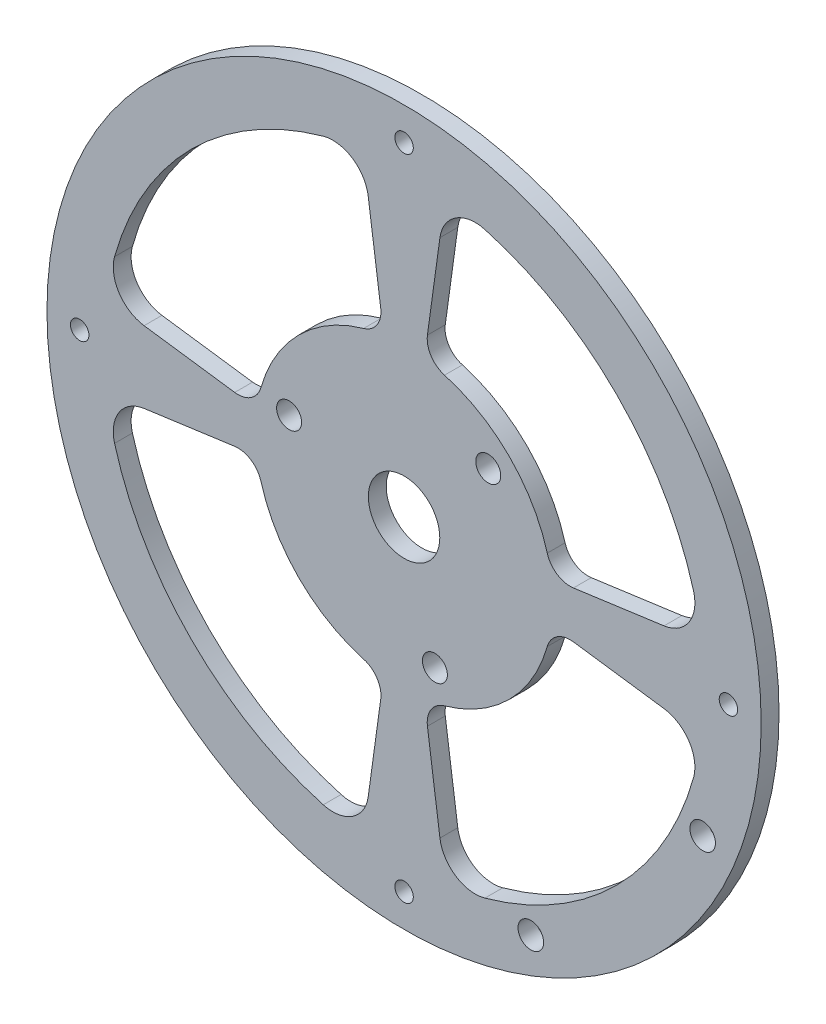
SolidWorks part; units mm, degrees
ref_plane "前视基准面" through (0, 0, 0) normal (0, 0, 1) x (1, 0, 0)
ref_plane "上视基准面" through (0, 0, 0) normal (0, 1, 0) x (1, 0, 0)
ref_plane "右视基准面" through (0, 0, 0) normal (1, 0, 0) x (0, 0, -1)
sketch "草图1" plane through (0, 0, 0) normal (0, 0, 1) x (1, 0, 0)
  line L0 (0, 0) -> (14.1421, 14.1421) construction
  line L1 (3.9232, -28.4536) -> (6.0227, -43.6804)
  line L2 (28.4536, 3.9232) -> (43.6804, 6.0227)
  line L3 (3.9232, 28.4536) -> (6.0227, 43.6804)
  line L4 (28.4536, -3.9232) -> (43.6804, -6.0227)
  line L5 (-28.4536, -3.9232) -> (-43.6804, -6.0227)
  line L6 (-3.9232, -28.4536) -> (-6.0227, -43.6804)
  line L7 (-3.9232, 28.4536) -> (-6.0227, 43.6804)
  line L8 (-28.4536, 3.9232) -> (-43.6804, 6.0227)
  circle A0 centre (0, 0) radius 60
  circle A1 centre (0, 54.5) radius 1.55
  circle A2 centre (-54.5, 0) radius 1.55
  circle A3 centre (0, -54.5) radius 1.55
  circle A4 centre (54.5, 0) radius 1.55
  arc A5 (48.6399, 13.5799) -> (13.5799, 48.6399) centre (0, 0) ccw
  circle A6 centre (0, 0) radius 20 construction
  circle A7 centre (14.1421, 14.1421) radius 2.1
  circle A8 centre (5.1764, -19.3185) radius 2.1
  circle A9 centre (-19.3185, 5.1764) radius 2.1
  circle A10 centre (0, 0) radius 6
  arc A11 (24.058, 6.798) -> (6.798, 24.058) centre (0, 0) ccw
  arc A12 (13.5799, 48.6399) -> (6.0227, 43.6804) centre (11.9665, 42.8609) ccw
  arc A13 (48.6399, 13.5799) -> (43.6804, 6.0227) centre (42.8609, 11.9665) cw
  arc A14 (3.9232, 28.4536) -> (6.798, 24.058) centre (7.8857, 27.9073) ccw
  arc A15 (28.4536, 3.9232) -> (24.058, 6.798) centre (27.9073, 7.8857) cw
  arc A16 (28.4536, -3.9232) -> (24.058, -6.798) centre (27.9073, -7.8857) ccw
  arc A17 (6.798, -24.058) -> (24.058, -6.798) centre (0, 0) ccw
  arc A18 (3.9232, -28.4536) -> (6.798, -24.058) centre (7.8857, -27.9073) cw
  arc A19 (13.5799, -48.6399) -> (6.0227, -43.6804) centre (11.9665, -42.8609) cw
  arc A20 (13.5799, -48.6399) -> (48.6399, -13.5799) centre (0, 0) ccw
  arc A21 (48.6399, -13.5799) -> (43.6804, -6.0227) centre (42.8609, -11.9665) ccw
  arc A22 (-3.9232, -28.4536) -> (-6.798, -24.058) centre (-7.8857, -27.9073) ccw
  arc A23 (-24.058, -6.798) -> (-6.798, -24.058) centre (0, 0) ccw
  arc A24 (-28.4536, -3.9232) -> (-24.058, -6.798) centre (-27.9073, -7.8857) cw
  arc A25 (-48.6399, -13.5799) -> (-43.6804, -6.0227) centre (-42.8609, -11.9665) cw
  arc A26 (-48.6399, -13.5799) -> (-13.5799, -48.6399) centre (0, 0) ccw
  arc A27 (-13.5799, -48.6399) -> (-6.0227, -43.6804) centre (-11.9665, -42.8609) ccw
  arc A28 (-28.4536, 3.9232) -> (-24.058, 6.798) centre (-27.9073, 7.8857) ccw
  arc A29 (-6.798, 24.058) -> (-24.058, 6.798) centre (0, 0) ccw
  arc A30 (-3.9232, 28.4536) -> (-6.798, 24.058) centre (-7.8857, 27.9073) cw
  arc A31 (-13.5799, 48.6399) -> (-6.0227, 43.6804) centre (-11.9665, 42.8609) cw
  arc A32 (-13.5799, 48.6399) -> (-48.6399, 13.5799) centre (0, 0) ccw
  arc A33 (-48.6399, 13.5799) -> (-43.6804, 6.0227) centre (-42.8609, 11.9665) ccw
  point P20 (0, 0)
  point P70 (0, 0)
  dimension "D1" = 3
  dimension "D2" = 4
extrude "凸台-拉伸1" add sketch "草图1" along normal blind 3
ref_axis "Axis1" through (0, 0, -0.15) along (0, 0, 1)
ref_plane "Plane1" through (0, 0, 0) normal (-0.7071, 0.7071, 0) x (0, 0, 1)
sketch "Sketch1" plane through (0, 0, 3) normal (0, 0, 1) x (1, 0, 0)
  line L0 (0, 0) -> (38.5373, -38.5373) construction
  line L2 (50.1675, -21.2948) -> (0, 0) construction
  line L3 (0, 0) -> (21.2948, -50.1675) construction
  line L4 (196.2221, -86.6206) -> (120.5617, -10.9602) construction
  circle A0 centre (0, 0) radius 54.5 construction
  circle A1 centre (50.1675, -21.2948) radius 2.15
  circle A2 centre (21.2948, -50.1675) radius 2.15
  dimension "D3" = 4.3
  dimension "D1" = 22
  dimension "D2" = 22
extrude "Cut-Extrude1" cut sketch "Sketch1" against normal blind 10
